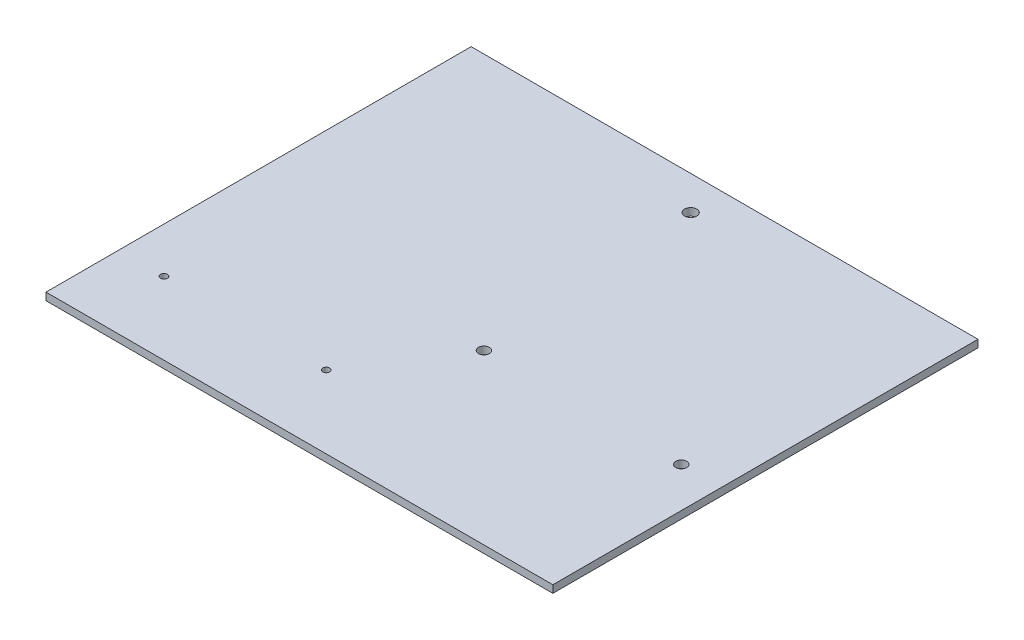
SolidWorks part; units mm, degrees
ref_plane "Front Plane" through (0, 0, 0) normal (0, 0, 1) x (1, 0, 0)
ref_plane "Top Plane" through (0, 0, 0) normal (0, 1, 0) x (1, 0, 0)
ref_plane "Right Plane" through (0, 0, 0) normal (1, 0, 0) x (0, 0, -1)
sketch "Sketch1" plane through (0, 0, 0) normal (0, 1, 0) x (1, 0, 0)
  line L1 (-94.869, -92.075) -> (94.869, -92.075)
  line L2 (-94.869, -92.075) -> (-94.869, 92.075)
  line L3 (-94.869, 92.075) -> (94.869, 92.075)
  line L4 (94.869, -92.075) -> (94.869, 92.075)
  line L5 (-94.869, -92.075) -> (94.869, 92.075) construction
  line L6 (-94.869, 92.075) -> (94.869, -92.075) construction
  point P0 (0, 0)
  dimension "D1" = 189.738
  dimension "D2" = 184.15
extrude "Boss-Extrude1" add sketch "Sketch1" along normal blind 2.794
sketch "Sketch2" plane through (0, 2.794, 0) normal (0, 1, 0) x (1, 0, 0)
  line L2 (94.869, 92.075) -> (-94.869, 92.075) construction
  circle A0 centre (0, 79.375) radius 2.286
  point P5 (0, 92.075)
  dimension "D1" = 4.572
  dimension "D2" = 12.7
extrude "Cut-Extrude1" cut sketch "Sketch2" against normal through all
sketch "Sketch3" plane through (0, 2.794, 0) normal (0, 1, 0) x (1, 0, 0)
  line L0 (0, -92.075) -> (-94.869, -92.075)
  line L1 (-94.869, -92.075) -> (94.869, -92.075) construction
  line L2 (-94.869, -92.075) -> (-94.869, -67.075)
  line L3 (-94.869, -67.075) -> (94.869, -67.075)
  line L4 (94.869, -67.075) -> (94.869, -92.075)
  line L5 (94.869, -92.075) -> (0, -92.075)
  line L10 (94.869, -92.075) -> (94.869, 92.075) construction
  point P5 (-94.869, -92.075)
  point P8 (94.869, -92.075)
  point P9 (0, 0)
  point P10 (0, 0)
  dimension "D3" = 25
extrude "Cut-Extrude2" cut sketch "Sketch3" against normal through all
sketch "Sketch4" plane through (0, 2.794, 0) normal (0, 1, 0) x (1, 0, 0)
  line L5 (3.239, -47.075) -> (82.369, -47.075) construction
  line L6 (3.239, -47.075) -> (3.239, 24.925) construction
  line L11 (3.239, 24.925) -> (82.369, 24.925) construction
  line L12 (82.369, -47.075) -> (82.369, 24.925) construction
  line L16 (-12.369, 55.505) -> (-12.369, -47.075) construction
  line L17 (-12.369, 55.505) -> (-82.369, 55.505) construction
  line L18 (-82.369, 55.505) -> (-82.369, -47.075) construction
  line L19 (-12.369, -47.075) -> (-82.369, -47.075) construction
  line L20 (-12.369, 55.505) -> (-82.369, -47.075) construction
  line L21 (-82.369, 55.505) -> (-12.369, -47.075) construction
  line L23 (3.239, -47.075) -> (82.369, 24.925) construction
  line L25 (3.239, 24.925) -> (82.369, -47.075) construction
  line L26 (0, -88.5226) -> (0, 97.866) construction
  line L27 (-94.869, -92.075) -> (-94.869, 92.075) construction
  line L28 (94.869, -92.075) -> (94.869, 92.075) construction
  line L30 (94.869, -67.075) -> (-94.869, -67.075) construction
  circle A6 centre (-77.889, -39.875) radius 1.3
  circle A7 centre (-17.183, -39.875) radius 1.3
  circle A10 centre (79.894, -4.04) radius 2.0387
  circle A11 centre (6.014, -4.04) radius 2.0387
  point P1 (42.804, -11.075)
  point P28 (-47.369, 4.215)
  dimension "D9" = 12.5
  dimension "D10" = 12.5
  dimension "D11" = 20
  dimension "D23" = 2.6
  dimension "D24" = 7.2
  dimension "D25" = 4.48
  dimension "D4" = 60.706
  dimension "D3" = 72
  dimension "D8" = 43.035
  dimension "D6" = 4.0774
  dimension "D1" = 79.13
  dimension "D5" = 73.88
  dimension "D7" = 0.7363
  dimension "D20" = 102.58
  dimension "D21" = 70
extrude "Cut-Extrude4" cut sketch "Sketch4" against normal through all both and the other way through all contours A6 | A7 | A11 | A10
